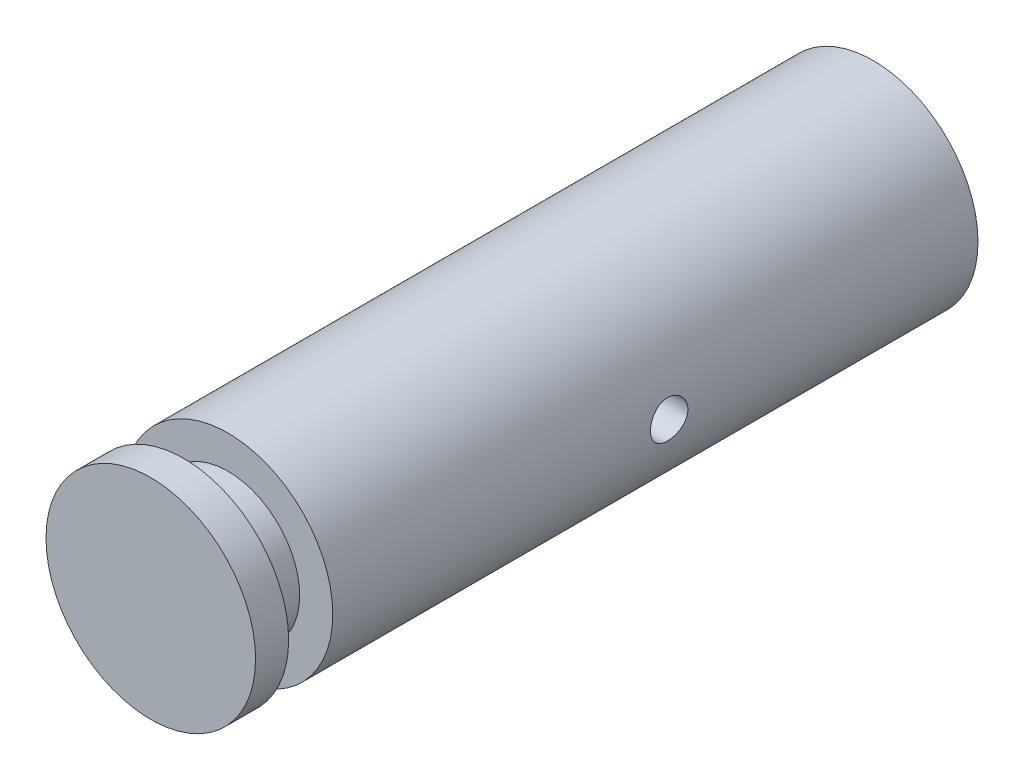
SolidWorks part; units mm, degrees
material "1.7225 (42CrMo4)"
ref_plane "E_Rechts" through (0, 0, 0) normal (0, 0, 1) x (1, 0, 0)
ref_plane "E_Oben" through (0, 0, 0) normal (0, 1, 0) x (1, 0, 0)
ref_plane "E_Vorne" through (0, 0, 0) normal (1, 0, 0) x (0, 0, -1)
ref_axis "E_Drehachse" through (0, 0, 61.5) along (0, 0, -1)
sketch "Skizze1" plane through (0, 0, 0) normal (0, 0, 1) x (1, 0, 0)
  circle A0 centre (0, 0) radius 19
  dimension "D1" = 38
extrude "Aufsatz-Linear austragen1" add sketch "Skizze1" along normal blind 75 and the other way blind 56
sketch "Skizze2" plane through (0, 0, 0) normal (1, 0, 0) x (0, 0, -1)
  line L1 (56, 19) -> (-75, 19) construction
  line L6 (-69, 19) -> (-61, 19)
  line L7 (-69, 19) -> (-69, 13)
  line L8 (-69, 13) -> (-61, 13)
  line L9 (-61, 19) -> (-61, 13)
  line L11 (0, 20.9) -> (0, -20.9) construction
  dimension "D1" = 6
  dimension "D2" = 8
  dimension "D3" = 61
revolve "Schnitt-Rotation1" cut sketch "Skizze2" angle 360 about axis through (0, 0, 61.5) along (0, 0, -1)
hole_wizard "M8 Gewindebohrung1" positions "Skizze3" profile "Skizze4" tap size "M8" standard "DIN"
sketch "Skizze3" plane through (0, 0, -56) normal (0, 0, -1) x (-1, 0, 0)
  point P0 (0, 0)
cosmetic thread "Bohrungsgewinde1" parameters "D1"=16, "D2"=8
sketch "Skizze4" plane through (0, 0, -56) normal (1, 0, 0) x (0, 1, 0)
  line L0 (0, 0) -> (0, 67.0429)
  line L1 (0, 67.0429) -> (3.4, 65)
  line L2 (3.4, 65) -> (3.4, 0)
  line L5 (3.4, 0) -> (0, 0)
  line L10 (0, 67.0429) -> (-3.4, 65) construction
  line L11 (0, -6.35) -> (0, 107.95) construction
  dimension "Bohrerdurchmesser" = 6.8
  dimension "Bohrungstiefe" = 65
  dimension "Spitzenwinkel" = 118
hole_wizard "Kernloch für M8 Gewinde1" positions "Skizze5" profile "Skizze7" hole size "M8" standard "DIN" end condition through all
sketch "Skizze5" plane through (0, 0, 0) normal (1, 0, 0) x (0, 0, -1)
  point P0 (0, 0)
sketch "Skizze7" plane through (0, 0, 0) normal (0, 1, 0) x (0, 0, 1)
  line L0 (0, 0) -> (0, 19)
  line L1 (0, 19) -> (3.4, 19)
  line L2 (3.4, 19) -> (3.4, 0)
  line L5 (3.4, 0) -> (0, 0)
  line L11 (0, -6.35) -> (0, 107.95) construction
  dimension "Bohrerdurchmesser" = 6.8
  dimension "Bohrungstiefe" = 19
mirror "Spiegeln1" about plane through (0, 0, 0) normal (1, 0, 0) of "Kernloch für M8 Gewinde1"
